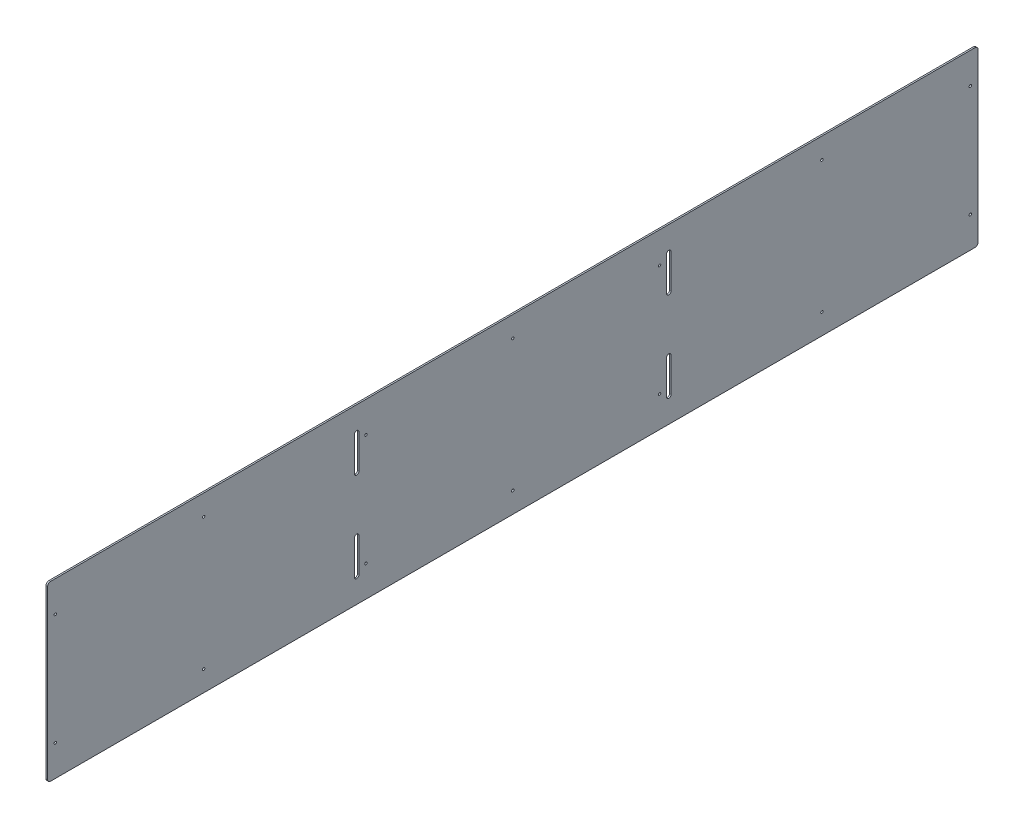
SolidWorks part; units mm, degrees
material "PC High Viscosity"
ref_plane "Front Plane" through (0, 0, 0) normal (0, 0, 1) x (1, 0, 0)
ref_plane "Top Plane" through (0, 0, 0) normal (0, 1, 0) x (1, 0, 0)
ref_plane "Right Plane" through (0, 0, 0) normal (1, 0, 0) x (0, 0, -1)
sketch "Sketch1" plane through (0, 0, 0) normal (1, 0, 0) x (0, 0, -1)
  line L1 (0, 0) -> (1911.35, 0)
  line L2 (0, 0) -> (0, 355.6)
  line L3 (0, 355.6) -> (1911.35, 355.6)
  line L4 (1911.35, 0) -> (1911.35, 355.6)
  dimension "D1" = 1911.35
  dimension "D2" = 355.6
extrude "Boss-Extrude1" add sketch "Sketch1" along normal blind 3.175
sketch "Sketch2" plane through (3.175, 0, 0) normal (1, 0, 0) x (0, 0, -1)
  line L0 (1911.35, 355.6) -> (0, 355.6) construction
  line L1 (0, 355.6) -> (0, 0) construction
  line L2 (0, 0) -> (1911.35, 0) construction
  line L3 (955.675, 313.182) -> (955.675, 42.418) construction
  circle A0 centre (15.875, 292.1) radius 2.4511
  circle A1 centre (654.05, 292.1) radius 2.4511
  circle A4 centre (320.675, 313.182) radius 2.4511
  circle A5 centre (955.675, 313.182) radius 2.4511
  circle A6 centre (1590.675, 313.182) radius 2.4511
  circle A7 centre (955.675, 42.418) radius 2.4511
  circle A8 centre (1590.675, 42.418) radius 2.4511
  circle A9 centre (320.675, 42.418) radius 2.4511
  circle A10 centre (15.875, 63.5) radius 2.4511
  circle A11 centre (654.05, 63.5) radius 2.4511
  circle A14 centre (1292.225, 292.1) radius 2.4511 [skipped]
  circle A15 centre (1930.4, 292.1) radius 2.4511 [skipped]
  circle A16 centre (1895.475, 63.5) radius 2.4511
  circle A17 centre (1895.475, 292.1) radius 2.4511
  circle A18 centre (1257.3, 63.5) radius 2.4511
  circle A19 centre (1257.3, 292.1) radius 2.4511
  point P34 (0, 0)
  point P35 (0, 0)
  dimension "D2" = 4.9022
  dimension "D4" = 4
  dimension "D6" = 4.9022
  dimension "D1" = 63.5
  dimension "D3" = 15.875
  dimension "D5" = 320.675
  dimension "D7" = 42.418
  dimension "D10" = 42.418
  dimension "D11" = 635
  dimension "D13" = 638.175
  dimension "D14" = 228.6
  dimension "D15" = 270.764
  dimension "D8" = 3
  dimension "D9" = 2
  dimension "D12" = 2
extrude "Cut-Extrude1" cut sketch "Sketch2" against normal through all
fillet "Fillet1" radius 6.35 4 edges at (1.5875, 0, -1911.35) (1.5875, 355.6, -1911.35) (1.5875, 0, 0) (1.5875, 355.6, 0)
sketch "Sketch3" plane through (3.175, 0, 0) normal (1, 0, 0) x (0, 0, -1)
  line L0 (654.05, 292.1) -> (654.05, 63.5) construction
  line L1 (1257.3, 292.1) -> (1257.3, 63.5) construction
  line L2 (635, 304.8) -> (635, 234.95) construction
  line L3 (639.7625, 304.8) -> (639.7625, 234.95)
  line L4 (630.2375, 304.8) -> (630.2375, 234.95)
  line L5 (1276.35, 304.8) -> (1276.35, 234.95) construction
  line L6 (1281.1125, 304.8) -> (1281.1125, 234.95)
  line L7 (1271.5875, 304.8) -> (1271.5875, 234.95)
  line L8 (0, 177.8) -> (1911.35, 177.8) construction
  line L9 (0, 349.25) -> (0, 6.35) construction
  line L10 (1911.35, 6.35) -> (1911.35, 349.25) construction
  line L11 (1276.35, 50.8) -> (1276.35, 120.65) construction
  line L12 (1281.1125, 50.8) -> (1281.1125, 120.65)
  line L13 (1271.5875, 50.8) -> (1271.5875, 120.65)
  line L14 (635, 50.8) -> (635, 120.65) construction
  line L15 (639.7625, 50.8) -> (639.7625, 120.65)
  line L16 (630.2375, 50.8) -> (630.2375, 120.65)
  arc A0 (639.7625, 304.8) -> (630.2375, 304.8) centre (635, 304.8) ccw
  arc A1 (630.2375, 234.95) -> (639.7625, 234.95) centre (635, 234.95) ccw
  arc A2 (1281.1125, 304.8) -> (1271.5875, 304.8) centre (1276.35, 304.8) ccw
  arc A3 (1271.5875, 234.95) -> (1281.1125, 234.95) centre (1276.35, 234.95) ccw
  arc A4 (1281.1125, 50.8) -> (1271.5875, 50.8) centre (1276.35, 50.8) cw
  arc A5 (1271.5875, 120.65) -> (1281.1125, 120.65) centre (1276.35, 120.65) cw
  arc A6 (639.7625, 50.8) -> (630.2375, 50.8) centre (635, 50.8) cw
  arc A7 (630.2375, 120.65) -> (639.7625, 120.65) centre (635, 120.65) cw
  point P10 (635, 269.875)
  point P17 (1276.35, 269.875)
  point P30 (1276.35, 85.725)
  point P37 (635, 85.725)
  dimension "D1" = 12.7
  dimension "D2" = 69.85
  dimension "D3" = 19.05
  dimension "D4" = 9.525
  dimension "D5" = 9.525
  dimension "D6" = 19.05
extrude "Cut-Extrude2" cut sketch "Sketch3" against normal through all
